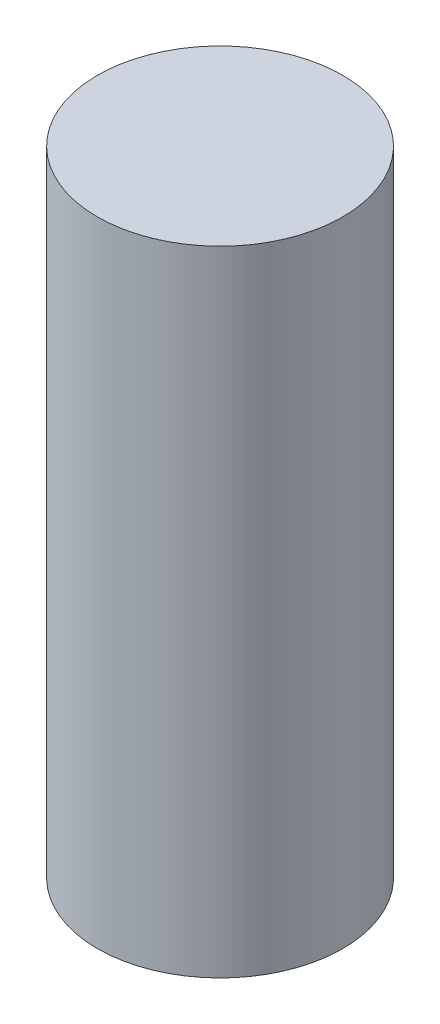
SolidWorks part; units mm, degrees
ref_plane "Front Plane" through (0, 0, 0) normal (0, 0, 1) x (1, 0, 0)
ref_plane "Top Plane" through (0, 0, 0) normal (0, 1, 0) x (1, 0, 0)
ref_plane "Right Plane" through (0, 0, 0) normal (1, 0, 0) x (0, 0, -1)
sketch "Sketch1" plane through (0, 0, 0) normal (0, 1, 0) x (1, 0, 0)
  circle A0 centre (0, 0) radius 6
  dimension "D1" = 12
extrude "Boss-Extrude1" add sketch "Sketch1" along normal blind 31
ref_axis "Axis1" through (0, 34.4242, 0) along (0, -1, 0)
